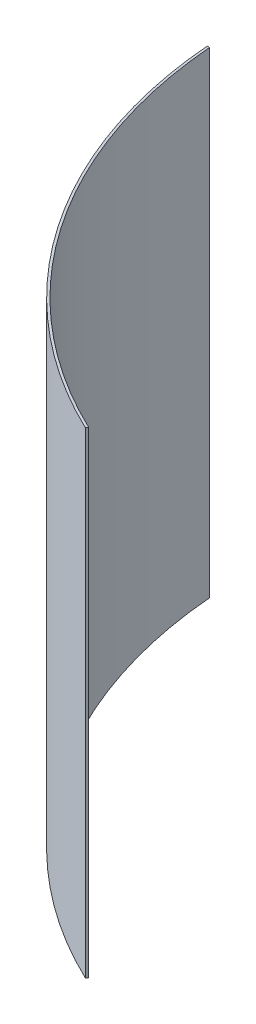
SolidWorks part; units mm, degrees
material "1060 Alloy"
ref_plane "Front Plane" through (0, 0, 0) normal (0, 0, 1) x (1, 0, 0)
ref_plane "Top Plane" through (0, 0, 0) normal (0, 1, 0) x (1, 0, 0)
ref_plane "Right Plane" through (0, 0, 0) normal (1, 0, 0) x (0, 0, -1)
sketch "Sketch1" plane through (0, 0, 0) normal (0, 1, 0) x (1, 0, 0)
  line L0 (-861.9527, -1815.8022) -> (-868.3277, -1823.844)
  line L1 (-2013.6591, -159.9282) -> (-2003.5072, -161.4282)
  arc A0 (-868.3277, -1823.844) -> (-2013.6591, -159.9282) centre (0, 0) cw
  arc A1 (-2003.5072, -161.4282) -> (-861.9527, -1815.8022) centre (0, 0) ccw
extrude "Boss-Extrude1" add sketch "Sketch1" along normal blind 2025.87
